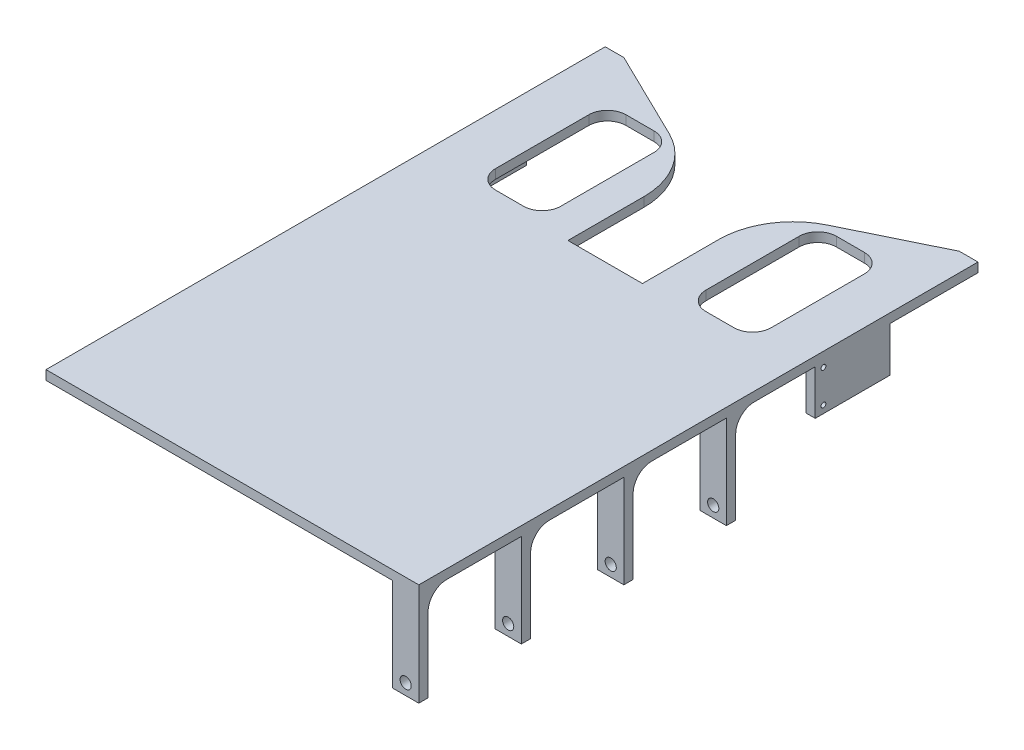
SolidWorks part; units mm, degrees
ref_plane "Front Plane" through (0, 0, 0) normal (0, 0, 1) x (1, 0, 0)
ref_plane "Top Plane" through (0, 0, 0) normal (0, 1, 0) x (1, 0, 0)
ref_plane "Right Plane" through (0, 0, 0) normal (1, 0, 0) x (0, 0, -1)
sketch "Sketch1" plane through (0, 0, 0) normal (0, 1, 0) x (1, 0, 0)
  line L0 (0, 0) -> (0, -300)
  line L1 (0, -300) -> (200, -300)
  line L2 (200, -300) -> (200, 0)
  line L3 (200, 0) -> (190, 0)
  line L4 (190, 0) -> (120, -34.1581)
  line L5 (120, -34.1581) -> (120, -100)
  line L6 (120, -100) -> (80, -100)
  line L7 (80, -100) -> (80, -34.1581)
  line L8 (80, -34.1581) -> (10, 0)
  line L9 (10, 0) -> (0, 0)
  line L10 (100, -300) -> (100, -100) construction
  point P9 (100, -100)
  dimension "D1" = 300
  dimension "D2" = 10
  dimension "D3" = 200
  dimension "D4" = 100
  dimension "D5" = 10
  dimension "D6" = 40
extrude "Boss-Extrude1" add sketch "Sketch1" along normal blind 5
sketch "Sketch2" plane through (0, 0, 0) normal (0, -1, 0) x (1, 0, 0)
  line L0 (0, 0) -> (0, 300) construction
  line L1 (0, 87.3209) -> (5, 87.3209)
  line L2 (0, 87.3209) -> (0, 47.3209)
  line L3 (0, 47.3209) -> (5, 47.3209)
  line L4 (5, 87.3209) -> (5, 47.3209)
  line L5 (200, 300) -> (200, 0) construction
  line L6 (200, 87.3209) -> (195, 87.3209)
  line L7 (200, 87.3209) -> (200, 47.3209)
  line L8 (200, 47.3209) -> (195, 47.3209)
  line L9 (195, 87.3209) -> (195, 47.3209)
  dimension "D1" = 5
  dimension "D2" = 40
  dimension "D3" = 5
extrude "Boss-Extrude2" add sketch "Sketch2" along normal blind 24
sketch "Sketch3" plane through (200, 0, 0) normal (1, 0, 0) x (0, 0, -1)
  line L4 (-47.3209, 0) -> (-87.3209, 0)
  line L5 (-47.3209, -24) -> (-47.3209, 0)
  line L6 (-87.3209, -24) -> (-47.3209, -24)
  line L7 (-87.3209, 0) -> (-87.3209, -24)
  line L8 (-47.3209, 0) -> (-87.3209, 0)
  line L9 (-47.3209, -24) -> (-47.3209, 0)
  line L10 (-87.3209, -24) -> (-47.3209, -24)
  line L11 (-87.3209, 0) -> (-87.3209, -24)
  circle A0 centre (-82.9, -2.5) radius 1.3 construction
  circle A1 centre (-82.9, -20) radius 1.3 construction
  circle A2 centre (-82.9, -2.5) radius 1.3
  circle A3 centre (-82.9, -20) radius 1.3
  dimension "D1" = 0
extrude "Cut-Extrude2" cut sketch "Sketch3" against normal through all contours A3 | A2
sketch "Sketch4" plane through (0, 5, 0) normal (0, 1, 0) x (1, 0, 0)
  line L0 (200, 0) -> (190, 0) construction
  line L1 (175.0541, -26) -> (140.0541, -26)
  line L2 (175.0541, -26) -> (175.0541, -96)
  line L3 (175.0541, -96) -> (140.0541, -96)
  line L4 (140.0541, -26) -> (140.0541, -96)
  line L5 (62.176, -26) -> (27.176, -26)
  line L6 (62.176, -26) -> (62.176, -96)
  line L7 (62.176, -96) -> (27.176, -96)
  line L8 (27.176, -26) -> (27.176, -96)
  dimension "D1" = 35
  dimension "D2" = 35
  dimension "D3" = 26
  dimension "D4" = 70
extrude "Cut-Extrude3" cut sketch "Sketch4" against normal up to next
fillet "Fillet1" radius 10 8 edges at (27.176, 2.5, 26) (27.176, 2.5, 96) (62.176, 2.5, 96) (62.176, 2.5, 26) (140.0541, 2.5, 96) (175.0541, 2.5, 96) (175.0541, 2.5, 26) (140.0541, 2.5, 26)
fillet "Fillet2" radius 40 2 edges at (120, 2.5, 34.1581) (80, 2.5, 34.1581)
sketch "Sketch5" plane through (0, 0, 0) normal (0, -1, 0) x (1, 0, 0)
  line L0 (200, 300) -> (200, 87.3209) construction
  line L1 (200, 295) -> (185.8997, 295)
  line L2 (200, 295) -> (200, 300)
  line L3 (200, 300) -> (185.8997, 300)
  line L4 (185.8997, 295) -> (185.8997, 300)
  line L5 (0, 300) -> (200, 300) construction
  line L6 (200, 240) -> (185.8997, 240)
  line L7 (200, 240) -> (200, 245)
  line L8 (200, 245) -> (185.8997, 245)
  line L9 (185.8997, 240) -> (185.8997, 245)
  line L10 (200, 185) -> (185.8997, 185)
  line L11 (200, 185) -> (200, 190)
  line L12 (200, 190) -> (185.8997, 190)
  line L13 (185.8997, 185) -> (185.8997, 190)
  line L14 (200, 130) -> (185.8997, 130)
  line L15 (200, 130) -> (200, 135)
  line L16 (200, 135) -> (185.8997, 135)
  line L17 (185.8997, 130) -> (185.8997, 135)
  dimension "D1" = 5
  dimension "D2" = 5
  dimension "D3" = 5
  dimension "D4" = 5
  dimension "D5" = 50
  dimension "D6" = 50
  dimension "D7" = 50
extrude "Boss-Extrude3" add sketch "Sketch5" along normal blind 50
fillet "Fillet3" radius 10 4 edges at (192.9498, 0, 130) (192.9498, 0, 185) (192.9498, 0, 240) (192.9498, 0, 295)
sketch "Sketch6" plane through (0, 0, 300) normal (0, 0, 1) x (1, 0, 0)
  line L0 (200, -50) -> (185.8997, -50) construction
  circle A0 centre (192.9498, -44) radius 3
  point P2 (0, 0)
  point P5 (192.9498, -50)
  dimension "D1" = 6
  dimension "D2" = 6
extrude "Cut-Extrude4" cut sketch "Sketch6" against normal through all
